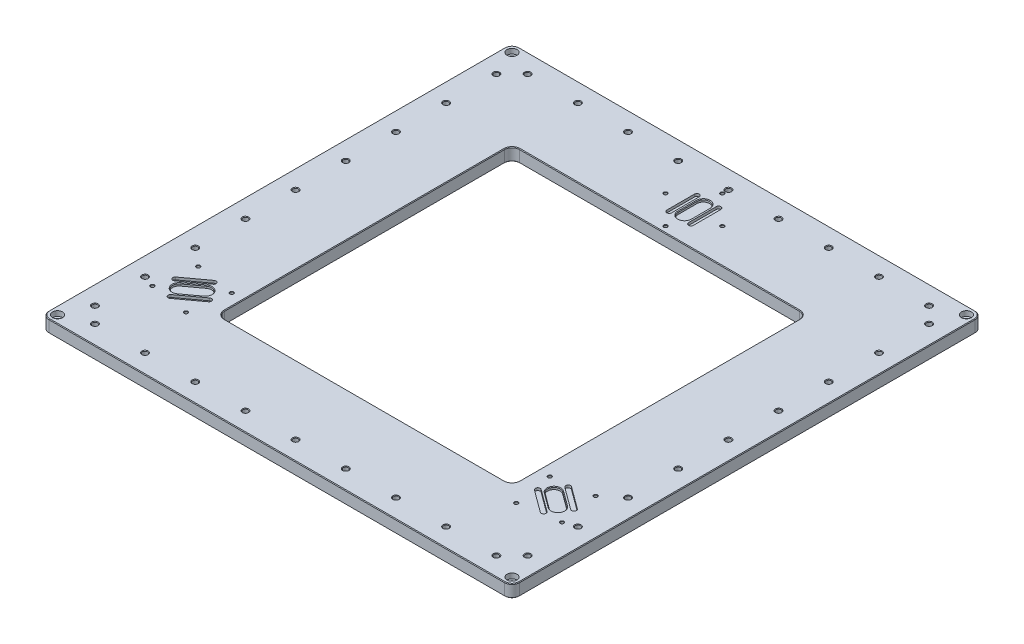
SolidWorks part; units mm, degrees
material "AISI 1045 Steel, cold drawn"
ref_plane "Front Plane" through (0, 0, 0) normal (0, 0, 1) x (1, 0, 0)
ref_plane "Top Plane" through (0, 0, 0) normal (0, 1, 0) x (1, 0, 0)
ref_plane "Right Plane" through (0, 0, 0) normal (1, 0, 0) x (0, 0, -1)
sketch "Sketch1" plane through (0, 0, 0) normal (0, 1, 0) x (1, 0, 0)
  line L1 (-187.5, -187.5) -> (187.5, -187.5)
  line L2 (-187.5, -187.5) -> (-187.5, 187.5)
  line L3 (-187.5, 187.5) -> (187.5, 187.5)
  line L4 (187.5, -187.5) -> (187.5, 187.5)
  line L5 (-187.5, -187.5) -> (187.5, 187.5) construction
  line L6 (-187.5, 187.5) -> (187.5, -187.5) construction
  point P0 (0, 0)
  dimension "D1" = 375
extrude "Boss-Extrude1" add sketch "Sketch1" along normal blind 10
hole_wizard "CBORE for M4 SHCS1" positions "Sketch4" profile "Sketch3" counterbore size "M4" standard "ANSI Metric" end condition up to next
sketch "Sketch4" plane through (0, 10, 0) normal (0, 1, 0) x (1, 0, 0)
  line L0 (0, 0) -> (-181.1218, -181.1218) construction
  line L2 (0, 0) -> (-181.1218, 0) construction
  line L3 (-181.1218, 0) -> (-181.1218, -181.1218) construction
  circle A0 centre (0, 0) radius 256.1449
  point P7 (-181.1218, -181.1218)
  dimension "D1" = 45
  dimension "D2" = 181.1218
sketch "Sketch3" plane through (-181.1218, 10, 181.1218) normal (1, 0, 0) x (0, 0, 1)
  line L0 (0, 0) -> (0, 10)
  line L1 (0, 10) -> (2.15, 10)
  line L3 (2.15, 10) -> (2.15, 4)
  line L4 (2.15, 4) -> (4, 4)
  line L5 (4, 4) -> (4, 0)
  line L7 (4, 0) -> (0, 0)
  line L11 (0, -6.35) -> (0, 107.95) construction
  dimension "Thru Hole Dia." = 4.3
  dimension "Thru Hole Depth" = 10
  dimension "C'Bore Dia." = 8
  dimension "C'Bore Depth" = 4
ref_axis "Axis1" through (0, 10.0013, 0) along (0, -1, 0)
hole_wizard "M5x0.8 Tapped Hole1" positions "Sketch15" profile "Sketch16" tap size "M5x0.8" standard "ANSI Metric" end condition up to next
sketch "Sketch15" plane through (0, 10, 0) normal (0, 1, 0) x (1, 0, 0)
  line L1 (172.5, -172.5) -> (-172.5, -172.5)
  line L2 (172.5, -172.5) -> (172.5, 172.5)
  line L3 (172.5, 172.5) -> (-172.5, 172.5)
  line L4 (-172.5, -172.5) -> (-172.5, 172.5)
  line L5 (172.5, -172.5) -> (-172.5, 172.5) construction
  line L6 (172.5, 172.5) -> (-172.5, -172.5) construction
  line L9 (152, -152) -> (-152, -152) construction
  line L10 (152, -152) -> (152, 152) construction
  line L11 (152, 152) -> (-152, 152) construction
  line L12 (-152, -152) -> (-152, 152) construction
  line L13 (152, -152) -> (-152, 152) construction
  line L14 (152, 152) -> (-152, -152) construction
  point P1 (0, 0)
  point P86 (0, 0)
  point P191 (-160, 172.5)
  point P197 (-120, 172.5)
  point P198 (-80, 172.5)
  point P199 (-40, 172.5)
  point P200 (0, 172.5)
  point P201 (40, 172.5)
  point P202 (80, 172.5)
  point P203 (120, 172.5)
  point P204 (160, 172.5)
  dimension "D1" = 345
  dimension "D2" = 304
  dimension "D4" = 40
  dimension "D3" = 9
cosmetic thread "Hole Thread1" parameters "D2"=5
cosmetic thread "Hole Thread2" parameters "D2"=5
cosmetic thread "Hole Thread3" parameters "D2"=5
cosmetic thread "Hole Thread4" parameters "D2"=5
cosmetic thread "Hole Thread5" parameters "D2"=5
cosmetic thread "Hole Thread6" parameters "D2"=5
cosmetic thread "Hole Thread7" parameters "D2"=5
cosmetic thread "Hole Thread8" parameters "D2"=5
cosmetic thread "Hole Thread9" parameters "D2"=5
sketch "Sketch16" plane through (0, 10, 0) normal (1, 0, 0) x (0, 0, 1)
  line L0 (0, 0) -> (0, 10)
  line L1 (0, 10) -> (2.525, 10)
  line L2 (2.1, 9.575) -> (2.1, 0.425)
  line L3 (2.1, 0.425) -> (2.525, 0)
  line L5 (2.525, 0) -> (0, 0)
  line L6 (-2.1, 0.425) -> (-2.525, 0) construction
  line L7 (2.525, 10) -> (2.1, 9.575)
  line L8 (-2.525, 10) -> (-2.1, 9.575) construction
  line L11 (0, -6.35) -> (0, 107.95) construction
  dimension "Thru Tap Drill Dia." = 4.2
  dimension "Thru Tap Drill Depth" = 10
  dimension "Near C'Sink Dia." = 5.05
  dimension "Near C'Sink Angle" = 90
  dimension "Far C'Sink Dia." = 5.05
  dimension "Far C'Sink Angle" = 90
pattern_circular "CirPattern1" count 4 over 360 about axis through (0, 10.0013, 0) along (0, -1, 0) of "CBORE for M4 SHCS1", "M5x0.8 Tapped Hole1"
cosmetic thread "Hole Thread12" parameters "D2"=5
cosmetic thread "Hole Thread13" parameters "D2"=5
cosmetic thread "Hole Thread14" parameters "D2"=5
cosmetic thread "Hole Thread15" parameters "D2"=5
cosmetic thread "Hole Thread16" parameters "D2"=5
cosmetic thread "Hole Thread17" parameters "D2"=5
cosmetic thread "Hole Thread18" parameters "D2"=5
cosmetic thread "Hole Thread19" parameters "D2"=5
cosmetic thread "Hole Thread20" parameters "D2"=5
cosmetic thread "Hole Thread21" parameters "D2"=5
cosmetic thread "Hole Thread22" parameters "D2"=5
cosmetic thread "Hole Thread23" parameters "D2"=5
cosmetic thread "Hole Thread24" parameters "D2"=5
cosmetic thread "Hole Thread25" parameters "D2"=5
cosmetic thread "Hole Thread26" parameters "D2"=5
cosmetic thread "Hole Thread27" parameters "D2"=5
cosmetic thread "Hole Thread28" parameters "D2"=5
cosmetic thread "Hole Thread29" parameters "D2"=5
cosmetic thread "Hole Thread30" parameters "D2"=5
cosmetic thread "Hole Thread31" parameters "D2"=5
cosmetic thread "Hole Thread32" parameters "D2"=5
cosmetic thread "Hole Thread33" parameters "D2"=5
cosmetic thread "Hole Thread34" parameters "D2"=5
cosmetic thread "Hole Thread35" parameters "D2"=5
cosmetic thread "Hole Thread36" parameters "D2"=5
cosmetic thread "Hole Thread37" parameters "D2"=5
cosmetic thread "Hole Thread38" parameters "D2"=5
sketch "Bed Holes" plane through (0, 10, 0) normal (0, 1, 0) x (1, 0, 0)
  line L0 (145, -110) -> (-145, -110) construction
  line L1 (0, -110) -> (0, 145) construction
  line L2 (152, 152) -> (152, -152) construction
  line L3 (152, 152) -> (-152, 152) construction
  line L4 (-152, 152) -> (-152, -152) construction
  line L5 (-152, -152) -> (152, -152) construction
  point P4 (0, -110)
  point P13 (0, -152)
  point P14 (152, 0)
  dimension "D1" = 255
  dimension "D2" = 7
  dimension "D3" = 304
  dimension "D4" = 7
sketch "Sketch7" plane through (0, 10, 0) normal (0, 1, 0) x (1, 0, 0)
  line L0 (-145, -110) -> (0, 145) construction
  line L1 (0, 145) -> (145, -110) construction
  line L2 (145, -110) -> (-145, -110) construction
  line L3 (-139.8734, -116.9798) -> (-150.1266, -103.0202) construction
  line L4 (-158.9922, -109.5319) -> (-141.2611, -96.5085) construction
  line L5 (-160.1259, -107.9884) -> (-142.3948, -94.965)
  line L8 (-157.8585, -111.0754) -> (-140.1274, -98.052)
  line L12 (-148.7389, -123.4915) -> (-131.0078, -110.4681) construction
  line L13 (-149.8726, -121.948) -> (-132.1415, -108.9246)
  line L14 (0, -110) -> (0, 145) construction
  line L16 (-145, -110) -> (0, -3.4986) construction
  line L17 (0, -3.4986) -> (0, 145) construction
  line L19 (145, -110) -> (0, -3.4986) construction
  line L20 (-147.6052, -125.035) -> (-129.8741, -112.0116)
  line L21 (0, -3.4986) -> (0, -110) construction
  line L23 (158.9922, -109.5319) -> (141.2611, -96.5085) construction
  line L24 (160.1259, -107.9884) -> (142.3948, -94.965)
  line L25 (157.8585, -111.0754) -> (140.1274, -98.052)
  line L26 (148.7389, -123.4915) -> (131.0078, -110.4681) construction
  line L27 (149.8726, -121.948) -> (132.1415, -108.9246)
  line L28 (147.6052, -125.035) -> (129.8741, -112.0116)
  line L29 (8.6603, 145) -> (-8.6603, 145) construction
  line L30 (-8.6603, 156) -> (-8.6603, 134) construction
  line L31 (-6.7451, 156) -> (-6.7451, 134)
  line L32 (-10.5754, 156) -> (-10.5754, 134)
  line L33 (8.6603, 156) -> (8.6603, 134) construction
  line L34 (10.5754, 156) -> (10.5754, 134)
  line L35 (6.7451, 156) -> (6.7451, 134)
  arc A0 (-160.1259, -107.9884) -> (-157.8585, -111.0754) centre (-158.9922, -109.5319) ccw
  arc A1 (-140.1274, -98.052) -> (-142.3948, -94.965) centre (-141.2611, -96.5085) ccw
  arc A2 (-149.8726, -121.948) -> (-147.6052, -125.035) centre (-148.7389, -123.4915) ccw
  arc A3 (-129.8741, -112.0116) -> (-132.1415, -108.9246) centre (-131.0078, -110.4681) ccw
  arc A4 (160.1259, -107.9884) -> (157.8585, -111.0754) centre (158.9922, -109.5319) cw
  arc A5 (140.1274, -98.052) -> (142.3948, -94.965) centre (141.2611, -96.5085) cw
  arc A6 (149.8726, -121.948) -> (147.6052, -125.035) centre (148.7389, -123.4915) cw
  arc A7 (129.8741, -112.0116) -> (132.1415, -108.9246) centre (131.0078, -110.4681) cw
  arc A8 (-6.7451, 156) -> (-10.5754, 156) centre (-8.6603, 156) ccw
  arc A9 (-10.5754, 134) -> (-6.7451, 134) centre (-8.6603, 134) ccw
  arc A10 (10.5754, 156) -> (6.7451, 156) centre (8.6603, 156) ccw
  arc A11 (6.7451, 134) -> (10.5754, 134) centre (8.6603, 134) ccw
  point P5 (-150.1266, -103.0202)
  point P8 (-145, -110)
  point P17 (-139.8734, -116.9798)
  point P25 (150.1266, -103.0202)
  point P33 (139.8734, -116.9798)
  point P41 (0, 145)
  point P43 (-8.6603, 145)
  point P49 (8.6603, 145)
  dimension "D4" = 22
  dimension "D3" = 1.9151
  dimension "D1" = 36.297
  dimension "D2" = 17.3205
extrude "Cut-Extrude2" cut sketch "Sketch7" against normal blind 2
sketch "Sketch5" plane through (0, 10, 0) normal (0, 1, 0) x (1, 0, 0)
  line L1 (117.5, -117.5) -> (-117.5, -117.5)
  line L2 (117.5, -117.5) -> (117.5, 117.5)
  line L3 (117.5, 117.5) -> (-117.5, 117.5)
  line L4 (-117.5, -117.5) -> (-117.5, 117.5)
  line L5 (117.5, -117.5) -> (-117.5, 117.5) construction
  line L6 (117.5, 117.5) -> (-117.5, -117.5) construction
  point P0 (0, 0)
  dimension "D1" = 235
extrude "Cut-Extrude3" cut sketch "Sketch5" against normal up to surface (10 mm away) up to face at (-172.5, 0, 162.525)
sketch "Sketch11" plane through (0, 10, 0) normal (0, 1, 0) x (1, 0, 0)
  line L0 (22.6274, 145) -> (0, 122.3726)
  line L1 (-131.6052, -128.2368) -> (-163.2368, -123.3948)
  line L2 (-131.6052, -128.2368) -> (-126.7632, -96.6052)
  line L3 (-126.7632, -96.6052) -> (-158.3948, -91.7632)
  line L4 (-163.2368, -123.3948) -> (-158.3948, -91.7632)
  line L5 (-131.6052, -128.2368) -> (-158.3948, -91.7632) construction
  line L6 (-126.7632, -96.6052) -> (-163.2368, -123.3948) construction
  line L7 (163.2368, -123.3948) -> (131.6052, -128.2368)
  line L8 (163.2368, -123.3948) -> (158.3948, -91.7632)
  line L9 (158.3948, -91.7632) -> (126.7632, -96.6052)
  line L10 (131.6052, -128.2368) -> (126.7632, -96.6052)
  line L11 (163.2368, -123.3948) -> (126.7632, -96.6052) construction
  line L12 (158.3948, -91.7632) -> (131.6052, -128.2368) construction
  line L13 (22.6274, 145) -> (0, 167.6274)
  line L14 (0, 122.3726) -> (-22.6274, 145)
  line L15 (0, 167.6274) -> (-22.6274, 145)
  line L16 (22.6274, 145) -> (-22.6274, 145) construction
  line L17 (0, 122.3726) -> (0, 167.6274) construction
  line L18 (0, -110) -> (0, 145) construction
  line L19 (-132.1415, -108.9246) -> (-149.8726, -121.948) construction
  line L20 (149.8726, -121.948) -> (132.1415, -108.9246) construction
  point P0 (-145, -110)
  point P6 (145, -110)
  point P13 (0, 145)
  point P21 (0, 0)
  dimension "D1" = 32
hole_wizard "M3x0.5 Tapped Hole1" positions "Sketch12" profile "Sketch13" tap size "M3x0.5" standard "ANSI Metric" end condition up to next
sketch "Sketch12" plane through (0, 10, 0) normal (0, 1, 0) x (1, 0, 0)
  point P0 (-163.2368, -123.3948)
  point P3 (-126.7632, -96.6052)
  point P6 (126.7632, -96.6052)
  point P9 (163.2368, -123.3948)
  point P12 (0, 122.3726)
  point P15 (0, 167.6274)
  point P19 (-158.3948, -91.7632)
  point P22 (-131.6052, -128.2368)
  point P25 (131.6052, -128.2368)
  point P28 (158.3948, -91.7632)
  point P31 (22.6274, 145)
  point P34 (-22.6274, 145)
sketch "Sketch13" plane through (-163.2368, 10, 123.3948) normal (1, 0, 0) x (0, 0, 1)
  line L0 (0, 0) -> (0, 10)
  line L1 (0, 10) -> (1.25, 10)
  line L2 (1.25, 10) -> (1.25, 0.275)
  line L3 (1.25, 0.275) -> (1.525, 0)
  line L5 (1.525, 0) -> (0, 0)
  line L6 (-1.25, 0.275) -> (-1.525, 0) construction
  line L11 (0, -6.35) -> (0, 107.95) construction
  dimension "Thru Tap Drill Dia." = 2.5
  dimension "Thru Tap Drill Depth" = 10
  dimension "Near C'Sink Dia." = 3.05
  dimension "Near C'Sink Angle" = 90
cosmetic thread "Hole Thread39" parameters "D2"=3
cosmetic thread "Hole Thread40" parameters "D2"=3
cosmetic thread "Hole Thread41" parameters "D2"=3
cosmetic thread "Hole Thread42" parameters "D2"=3
cosmetic thread "Hole Thread43" parameters "D2"=3
cosmetic thread "Hole Thread44" parameters "D2"=3
cosmetic thread "Hole Thread45" parameters "D2"=3
cosmetic thread "Hole Thread46" parameters "D2"=3
cosmetic thread "Hole Thread47" parameters "D2"=3
cosmetic thread "Hole Thread48" parameters "D2"=3
cosmetic thread "Hole Thread49" parameters "D2"=3
cosmetic thread "Hole Thread50" parameters "D2"=3
sketch "Sketch14" plane through (0, 10, 0) normal (0, 1, 0) x (1, 0, 0)
  line L0 (-151.0447, -114.4398) -> (-138.9553, -105.5602) construction
  line L1 (-154.0045, -110.41) -> (-141.9152, -101.5304)
  line L2 (-148.0848, -118.4696) -> (-135.9955, -109.59)
  line L3 (151.0447, -114.4398) -> (138.9553, -105.5602) construction
  line L4 (148.0848, -118.4696) -> (135.9955, -109.59)
  line L5 (154.0045, -110.41) -> (141.9152, -101.5304)
  line L6 (0, 137.5) -> (0, 152.5) construction
  line L7 (-5, 137.5) -> (-5, 152.5)
  line L8 (5, 137.5) -> (5, 152.5)
  line L9 (-157.8585, -111.0754) -> (-140.1274, -98.052) construction
  line L10 (140.1274, -98.052) -> (157.8585, -111.0754) construction
  arc A3 (-154.0045, -110.41) -> (-148.0848, -118.4696) centre (-151.0447, -114.4398) ccw
  arc A4 (-135.9955, -109.59) -> (-141.9152, -101.5304) centre (-138.9553, -105.5602) ccw
  arc A5 (148.0848, -118.4696) -> (154.0045, -110.41) centre (151.0447, -114.4398) ccw
  arc A6 (141.9152, -101.5304) -> (135.9955, -109.59) centre (138.9553, -105.5602) ccw
  arc A7 (-5, 137.5) -> (5, 137.5) centre (0, 137.5) ccw
  arc A8 (5, 152.5) -> (-5, 152.5) centre (0, 152.5) ccw
  point P3 (-145, -110)
  point P12 (145, -110)
  point P20 (0, 145)
  dimension "D1" = 5
  dimension "D2" = 15
extrude "Cut-Extrude4" cut sketch "Sketch14" against normal blind 2
fillet "Fillet2" radius 6 8 edges at (-117.5, 5, 117.5) (117.5, 5, -117.5) (117.5, 5, 117.5) (-117.5, 5, -117.5) (187.5, 5, 187.5) (-187.5, 5, 187.5) (187.5, 5, -187.5) (-187.5, 5, -187.5)
chamfer "Chamfer1" distance 0.5 angle 45 44 edges at (0, 10, -132.5) (5, 10, -145) (-5, 10, -145) (0, 10, -157.5) (155.0745, 10, 117.3996) (147.9599, 10, 105.9702) (142.0401, 10, 114.0298) (134.9255, 10, 102.6004) (-134.9255, 10, 102.6004) (-147.9599, 10, 105.9702) (-142.0401, 10, 114.0298) (-155.0745, 10, 117.3996) (117.5, 0, 0) (115.7426, 0, -115.7426) (115.7426, 0, 115.7426) (0, 0, -117.5) (0, 0, 117.5) (-115.7426, 0, -115.7426) (-115.7426, 0, 115.7426) (-117.5, 0, 0) (117.5, 10, 0) (115.7426, 10, -115.7426) (115.7426, 10, 115.7426) (0, 10, -117.5) (0, 10, 117.5) (-115.7426, 10, -115.7426) (-115.7426, 10, 115.7426) (-117.5, 10, 0) (0, 0, -187.5) (-185.7426, 0, -185.7426) (185.7426, 0, -185.7426) (-187.5, 0, 0) (187.5, 0, 0) (-185.7426, 0, 185.7426) (185.7426, 0, 185.7426) (0, 0, 187.5) (0, 10, -187.5) (-185.7426, 10, -185.7426) (185.7426, 10, -185.7426) (-187.5, 10, 0) (187.5, 10, 0) (-185.7426, 10, 185.7426) (185.7426, 10, 185.7426) (0, 10, 187.5)
